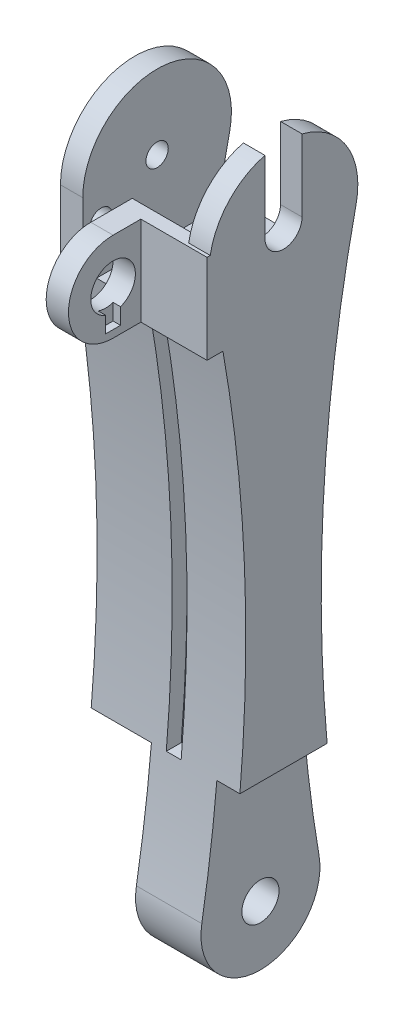
SolidWorks part; units mm, degrees
ref_plane "Front Plane" through (0, 0, 0) normal (0, 0, 1) x (1, 0, 0)
ref_plane "Top Plane" through (0, 0, 0) normal (0, 1, 0) x (1, 0, 0)
ref_plane "Right Plane" through (0, 0, 0) normal (1, 0, 0) x (0, 0, -1)
sketch "Sketch1" plane through (0, 0, 0) normal (1, 0, 0) x (0, 0, -1)
  arc A0 (9.7654, 20.1165) -> (-9.7654, 20.1165) centre (0, 22.2701) ccw
  arc A1 (-7.8874, -56.3924) -> (7.8874, -56.3924) centre (0, -57.7299) ccw
  arc A2 (-7.8874, -56.3924) -> (-9.7654, 20.1165) centre (-205.0724, -22.9549) ccw
  circle A3 centre (0, 22.2701) radius 1.5
  arc A4 (9.7654, 20.1165) -> (7.8874, -56.3924) centre (205.0724, -22.9549) ccw
  circle A5 centre (0, -57.7299) radius 2.5
extrude "Boss-Extrude1" add sketch "Sketch1" along normal blind 20
sketch "Sketch2" plane through (0, 0, 0) normal (0, 0, 1) x (1, 0, 0)
  line L1 (0, -65.7299) -> (8.1, -65.7299)
  line L2 (0, -65.7299) -> (0, -40.7299)
  line L3 (0, -40.7299) -> (8.1, -40.7299)
  line L4 (8.1, -65.7299) -> (8.1, -40.7299)
  line L5 (20, -65.7299) -> (16.9, -65.7299)
  line L6 (20, -65.7299) -> (20, -40.7299)
  line L7 (20, -40.7299) -> (16.9, -40.7299)
  line L8 (16.9, -65.7299) -> (16.9, -40.7299)
  line L11 (3, 32.2701) -> (8.1, 32.2701)
  line L12 (3, 32.2701) -> (3, 12.2701)
  line L13 (3, 12.2701) -> (8.1, 12.2701)
  line L14 (8.1, 32.2701) -> (8.1, 12.2701)
extrude "Cut-Extrude1" cut sketch "Sketch2" against normal blind 20 and the other way blind 20
sketch "Sketch3" plane through (8.1, 0, 0) normal (-1, 0, 0) x (0, 0, 1)
  line L0 (8.5, 22.2701) -> (8.5, 40.9095)
  line L1 (8.5, 40.9095) -> (-17.5287, 40.9095)
  line L2 (-17.5287, 40.9095) -> (-17.5287, 13.7701)
  line L3 (0, 13.7701) -> (-17.5287, 13.7701)
  arc A0 (0, 13.7701) -> (8.5, 22.2701) centre (0, 22.2701) ccw
extrude "Cut-Extrude2" cut sketch "Sketch3" against normal blind 9
sketch "Sketch4" plane through (8.1, 0, 0) normal (-1, 0, 0) x (0, 0, 1)
  line L0 (8.5, 27.5379) -> (8.2838, 12.7416)
  line L1 (8.2838, 12.7416) -> (10.2838, 12.7416)
  line L2 (10.2838, 12.7416) -> (10.2838, 27.5379)
  line L3 (10.2838, 27.5379) -> (8.5, 27.5379)
  arc A0 (9.7654, 20.1165) -> (5.8639, -40.7299) centre (205.0724, -22.9549) ccw construction
extrude "Boss-Extrude2" add sketch "Sketch4" against normal through all
sketch "Sketch5" plane through (8.1, 0, 0) normal (-1, 0, 0) x (0, 0, 1)
  line L4 (8.1452, 11.9686) -> (8.4478, 23.9686)
  line L6 (14.0224, 23.9686) -> (9.8547, 23.9686)
  line L8 (8.1452, 11.9686) -> (14.0224, 11.9686)
  line L9 (8.5, 27.5379) -> (8.4045, 20.9993) construction
  line L10 (8.4478, 23.9686) -> (9.8547, 23.9686)
  circle A2 centre (14.0224, 17.9686) radius 3
  arc A5 (14.0224, 11.9686) -> (14.0224, 23.9686) centre (14.0224, 17.9686) ccw
  arc A6 (9.7654, 20.1165) -> (-9.7654, 20.1165) centre (0, 22.2701) ccw construction
  arc A7 (9.7654, 20.1165) -> (5.8639, -40.7299) centre (205.0724, -22.9549) ccw construction
extrude "Boss-Extrude3" add sketch "Sketch5" against normal blind 3
sketch "Sketch12" plane through (11.1, 0, 0) normal (1, 0, 0) x (0, 0, -1)
  line L3 (-15.0224, 13.9686) -> (-15.0224, 12.9686)
  line L4 (-14.0224, 15.1402) -> (-15.0224, 15.1402)
  line L5 (-15.0224, 13.9686) -> (-15.0224, 15.1402)
  line L7 (-15.0224, 12.9686) -> (-13.0224, 12.9686)
  line L8 (-14.0224, 15.1402) -> (-13.0224, 15.1402)
  line L9 (-13.0224, 13.9686) -> (-13.0224, 15.1402)
  line L10 (-13.0224, 13.9686) -> (-13.0224, 12.9686)
  circle A0 centre (-14.0224, 17.9686) radius 3 construction
extrude "Cut-Extrude6" cut sketch "Sketch12" against normal blind 1
sketch "Sketch13" plane through (17.1, 0, 0) normal (-1, 0, 0) x (0, 0, 1)
  circle A0 centre (0, 22.2701) radius 2.5
extrude "Cut-Extrude7" cut sketch "Sketch13" against normal blind 4
sketch "Sketch10" plane through (17.1, 0, 0) normal (-1, 0, 0) x (0, 0, 1)
  line L0 (8.2838, 12.7416) -> (6.2515, 12.7416)
  line L1 (5.8639, -40.7299) -> (3.856, -40.7299)
  line L2 (5.8639, -40.7299) -> (-5.8639, -40.7299) construction
  line L3 (8.2838, 12.7416) -> (7.833, -40.7299)
  line L4 (7.833, -40.7299) -> (5.8639, -40.7299)
  arc A2 (6.3159, 13.0985) -> (3.8718, -40.9076) centre (205.0724, -22.9549) ccw
  arc A3 (6.2515, 12.7416) -> (3.856, -40.7299) centre (205.0724, -22.9549) ccw
  dimension "D1" = 2
extrude "Cut-Extrude5" cut sketch "Sketch10" along normal blind 2 from offset 5
sketch "Sketch14" plane through (0, 0, 0) normal (-1, 0, 0) x (0, 0, 1)
  circle A3 centre (7.5326, 18.3318) radius 1.5
extrude "Cut-Extrude8" cut sketch "Sketch14" against normal up to next
sketch "Sketch15" plane through (0, 0, 0) normal (-1, 0, 0) x (0, 0, 1)
  line L0 (10, 22.2701) -> (10, 11.9686)
  line L1 (8.1452, 11.9686) -> (14.0224, 11.9686) construction
  line L2 (10, 11.9686) -> (8.1452, 11.9686)
  line L3 (10, 22.2701) -> (7.5957, 11.9686)
  line L4 (7.5957, 11.9686) -> (8.1452, 11.9686)
  arc A0 (9.7654, 20.1165) -> (-9.7654, 20.1165) centre (0, 22.2701) ccw construction
extrude "Boss-Extrude4" add sketch "Sketch15" against normal blind 3
sketch "Sketch16" plane through (20, 0, 0) normal (1, 0, 0) x (0, 0, -1)
  line L0 (-10.2838, 23.9686) -> (-9.8547, 23.9686)
  line L1 (-10.2838, 23.9686) -> (-10.2838, 27.5379)
  line L2 (-10.2838, 27.5379) -> (-8.5, 27.5379) construction
  line L3 (-10.2838, 12.7416) -> (-10.2838, 27.5379) construction
  line L4 (-10.2838, 27.5379) -> (-8.5, 27.5379)
  arc A0 (-8.5, 27.5379) -> (-9.8547, 23.9686) centre (0, 22.2701) ccw
extrude "Cut-Extrude9" cut sketch "Sketch16" against normal blind 3
sketch "Sketch17" plane through (0, 0, 10.2838) normal (0, 0, 1) x (1, 0, 0)
  line L1 (17.1, 27.5379) -> (8.1, 27.5379)
  line L2 (17.1, 27.5379) -> (17.1, 23.9686)
  line L3 (17.1, 23.9686) -> (8.1, 23.9686)
  line L4 (8.1, 27.5379) -> (8.1, 23.9686)
extrude "Cut-Extrude11" cut sketch "Sketch17" against normal blind 3
sketch "Sketch18" plane through (11.1, 0, 0) normal (1, 0, 0) x (0, 0, -1)
  line L1 (-10.2838, 12.7416) -> (-4.5128, 12.7416)
  line L2 (-10.2838, 12.7416) -> (-10.2838, 11.9686)
  line L3 (-10.2838, 11.9686) -> (-4.5128, 11.9686)
  line L4 (-4.5128, 12.7416) -> (-4.5128, 11.9686)
extrude "Boss-Extrude5" add sketch "Sketch18" along normal through all and the other way blind 1
sketch "Sketch19" plane through (0, 12.2701, 0) normal (0, 1, 0) x (1, 0, 0)
  line L1 (8.1, -8.1989) -> (3, -8.1989)
  line L2 (8.1, -8.1989) -> (8.1, 8.1989)
  line L3 (8.1, 8.1989) -> (3, 8.1989)
  line L4 (3, -8.1989) -> (3, 8.1989)
extrude "Cut-Extrude12" cut sketch "Sketch19" against normal up to surface (0.3015 mm away) up to face at (1.5, 11.9686, 9.0726)
sketch "Sketch20" plane through (17.1, 0, 0) normal (-1, 0, 0) x (0, 0, 1)
  line L1 (2.5, 22.2701) -> (-2.5, 22.2701)
  line L2 (2.5, 22.2701) -> (2.5, 34.6894)
  line L3 (2.5, 34.6894) -> (-2.5, 34.6894)
  line L4 (-2.5, 22.2701) -> (-2.5, 34.6894)
  circle A0 centre (0, 22.2701) radius 2.5 construction
extrude "Cut-Extrude13" cut sketch "Sketch20" against normal blind 10
